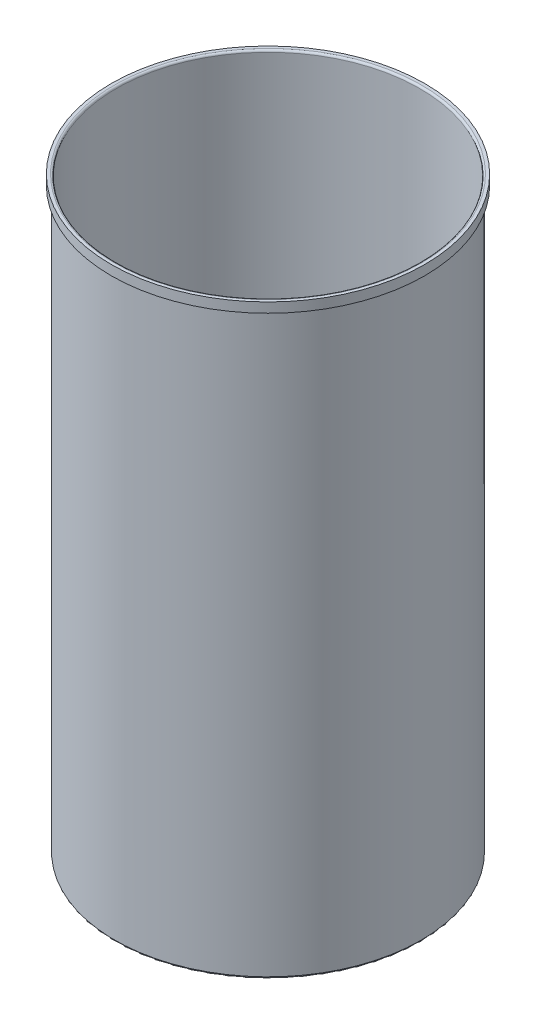
SolidWorks part; units mm, degrees
ref_plane "Front Plane" through (0, 0, 0) normal (0, 0, 1) x (1, 0, 0)
ref_plane "Top Plane" through (0, 0, 0) normal (0, 1, 0) x (1, 0, 0)
ref_plane "Right Plane" through (0, 0, 0) normal (1, 0, 0) x (0, 0, -1)
sketch "Sketch1" plane through (0, 0, 0) normal (0, 1, 0) x (1, 0, 0)
  circle A0 centre (0, 0) radius 196.85
  dimension "D1" = 393.7
sketch "Sketch2" plane through (0, 0, 0) normal (0, 0, 1) x (1, 0, 0)
  line L0 (196.85, 0) -> (196.85, 762)
  line L1 (196.85, 0) -> (-196.85, 0) construction
  line L2 (196.85, 0) -> (198.4375, 0)
  line L3 (198.4375, 0) -> (198.4375, 760.4125)
  line L4 (198.4375, 760.4125) -> (201.6125, 760.4125)
  line L5 (201.6125, 760.4125) -> (201.6125, 749.3)
  line L6 (201.6125, 749.3) -> (203.2, 749.3)
  line L7 (203.2, 749.3) -> (203.2, 762)
  line L8 (203.2, 762) -> (196.85, 762)
  dimension "D1" = 762
  dimension "D2" = 1.5875
  dimension "D3" = 1.5875
  dimension "D4" = 1.5875
  dimension "D5" = 3.175
  dimension "D6" = 12.7
sweep "Sweep1" add profiles "Sketch2" path "Sketch1"
sketch "Sketch3" plane through (0, 0, 0) normal (0, -1, 0) x (-1, 0, 0)
  circle A0 centre (0, 0) radius 198.4375
extrude "Boss-Extrude1" add sketch "Sketch3" along normal blind 1.5875
fillet "Fillet1" radius 2.54 2 edges at (0, -1.5875, -198.4375) (196.85, 762, 0)
